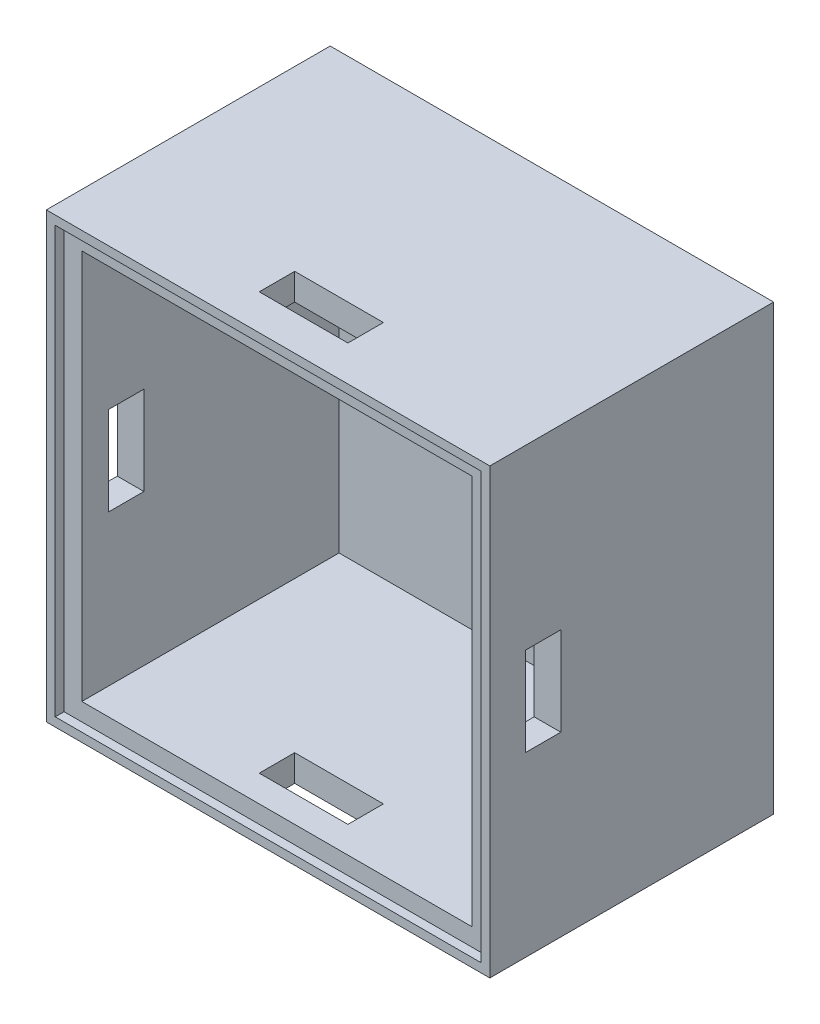
SolidWorks part; units mm, degrees
ref_plane "정면" through (0, 0, 0) normal (0, 0, 1) x (1, 0, 0)
ref_plane "윗면" through (0, 0, 0) normal (0, 1, 0) x (1, 0, 0)
ref_plane "우측면" through (0, 0, 0) normal (1, 0, 0) x (0, 0, -1)
sketch "스케치1" plane through (0, 0, 0) normal (0, 0, 1) x (1, 0, 0)
  line L1 (-125, 125) -> (125, 125)
  line L2 (-125, 125) -> (-125, -125)
  line L3 (-125, -125) -> (125, -125)
  line L4 (125, 125) -> (125, -125)
  line L5 (-125, 125) -> (125, -125) construction
  line L6 (-125, -125) -> (125, 125) construction
  point P0 (0, 0)
  dimension "D1" = 250
  dimension "D2" = 250
extrude "보스-돌출1" add sketch "스케치1" along normal blind 10 contours L1 L4 L3 L2
sketch "스케치2" plane through (0, 0, 0) normal (0, 0, -1) x (-1, 0, 0)
  line L1 (-50, 50) -> (50, 50)
  line L2 (-50, 50) -> (-50, -50)
  line L3 (-50, -50) -> (50, -50)
  line L4 (50, 50) -> (50, -50)
  line L5 (-50, 50) -> (50, -50) construction
  line L6 (-50, -50) -> (50, 50) construction
  line L7 (-127.5, 127.5) -> (127.5, 127.5)
  line L8 (-127.5, 127.5) -> (-127.5, -127.5)
  line L9 (-127.5, -127.5) -> (127.5, -127.5)
  line L10 (127.5, 127.5) -> (127.5, -127.5)
  line L11 (-127.5, 127.5) -> (127.5, -127.5) construction
  line L12 (-127.5, -127.5) -> (127.5, 127.5) construction
  line L13 (-107.5, 107.5) -> (107.5, 107.5)
  line L14 (-107.5, 107.5) -> (-107.5, -107.5)
  line L15 (-107.5, -107.5) -> (107.5, -107.5)
  line L16 (107.5, 107.5) -> (107.5, -107.5)
  line L17 (-107.5, 107.5) -> (107.5, -107.5) construction
  line L18 (-107.5, -107.5) -> (107.5, 107.5) construction
  point P0 (0, 0)
  point P6 (0, 0)
  point P11 (0, 0)
  line M3 (125, -125) -> (125, 125)
  line M4 (125, 125) -> (-125, 125)
  line M5 (-125, 125) -> (-125, -125)
  line M6 (-125, -125) -> (125, -125)
  dimension "D1" = 100
  dimension "D2" = 100
  dimension "D3" = 3.5355
  dimension "D4" = 20
  dimension "D5" = 20
extrude "보스-돌출2" add sketch "스케치2" along normal blind 5 contours L13 L16 L15 L14 M6 M3 M4 M5 | L4 L1 L2 L3 region at (0, 0, 0) region at (0, -121.4645, 0)
sketch "스케치3" plane through (0, 0, 10) normal (0, 0, 1) x (1, 0, 0)
  line L1 (-125, 125) -> (125, 125)
  line L2 (-125, 125) -> (-125, -125)
  line L3 (-125, -125) -> (125, -125)
  line L4 (125, 125) -> (125, -125)
  line L5 (-125, 125) -> (125, -125) construction
  line L6 (-125, -125) -> (125, 125) construction
  line L7 (-125, 125) -> (125, 125)
  line L8 (-125, 125) -> (-125, -125)
  line L9 (-125, -125) -> (125, -125)
  line L10 (125, 125) -> (125, -125)
  line L11 (-125, 125) -> (125, -125) construction
  line L12 (-125, -125) -> (125, 125) construction
  point P0 (0, 0)
  point P7 (0, 0)
  line M9 (-125, 125) -> (-125, -125)
  line M10 (-125, -125) -> (125, -125)
  line M11 (125, -125) -> (125, 125)
  line M12 (125, 125) -> (-125, 125)
  dimension "D1" = 250
extrude "보스-돌출3" add sketch "스케치3" along normal blind 150 contours M12 M9 M10 M11 region at (0, 0, 10)
sketch "스케치4" plane through (0, 0, 160) normal (0, 0, 1) x (1, 0, 0)
  line L1 (-110, 110) -> (110, 110)
  line L2 (-110, 110) -> (-110, -110)
  line L3 (-110, -110) -> (110, -110)
  line L4 (110, 110) -> (110, -110)
  line L5 (-110, 110) -> (110, -110) construction
  line L6 (-110, -110) -> (110, 110) construction
  point P0 (0, 0)
  dimension "D1" = 220
  dimension "D2" = 220
extrude "컷-돌출1" cut sketch "스케치4" against normal blind 150 contours L2 L3 L4 L1
sketch "스케치5" plane through (-125, 0, 0) normal (-1, 0, 0) x (0, 0, 1)
  text T0 "\r\n\r\n\r\nfront" font "Century Gothic" height 20
extrude "컷-돌출2" cut sketch "스케치5" against normal blind 4
ref_plane "평면1" through (0, 0, 150) normal (0, 0, -1) x (-1, 0, 0)
sketch "스케치6" plane through (-125, 0, 0) normal (-1, 0, 0) x (0, 0, 1)
  line L0 (160, -125) -> (-5, -125) construction
  line L1 (120, 25) -> (140, 25)
  line L2 (120, 25) -> (120, -25)
  line L3 (120, -25) -> (140, -25)
  line L4 (140, 25) -> (140, -25)
  line L5 (120, 25) -> (140, -25) construction
  line L6 (120, -25) -> (140, 25) construction
  line L7 (160, 125) -> (-5, 125) construction
  line L9 (160, 125) -> (160, -125) construction
  point P0 (130, 0)
  dimension "D1" = 100
  dimension "D2" = 100
  dimension "D3" = 20
  dimension "D4" = 20
extrude "컷-돌출3" cut sketch "스케치6" against normal through all
sketch "스케치7" plane through (0, 0, 0) normal (0, 1, 0) x (1, 0, 0)
  line L0 (0, 0) -> (0, -331.8175) construction
pattern_circular "원형 패턴1" count 2 every 90 about axis through (0, 0, 0) along (0, 0, 1) of "컷-돌출3" reverse direction yes
sketch "스케치11" plane through (0, 0, 160) normal (0, 0, 1) x (1, 0, 0)
  line L0 (125, 125) -> (-125, 125) construction
  line L1 (-120, 120) -> (120, 120)
  line L2 (-120, 120) -> (-120, -120)
  line L3 (-120, -120) -> (120, -120)
  line L4 (120, 120) -> (120, -120)
  line L5 (-120, 120) -> (120, -120) construction
  line L6 (-120, -120) -> (120, 120) construction
  line L7 (125, -125) -> (125, 125) construction
  point P0 (0, 0)
  dimension "D1" = 5
  dimension "D2" = 5
extrude "컷-돌출5" cut sketch "스케치11" against normal blind 5
sketch "스케치12" plane through (0, 0, -5) normal (0, 0, -1) x (-1, 0, 0)
  line L0 (125, 125) -> (-125, 125) construction
  line L1 (-120, 120) -> (120, 120)
  line L2 (-120, 120) -> (-120, -120)
  line L3 (-120, -120) -> (120, -120)
  line L4 (120, 120) -> (120, -120)
  line L5 (-120, 120) -> (120, -120) construction
  line L6 (-120, -120) -> (120, 120) construction
  line L7 (-125, 125) -> (-125, -125) construction
  point P0 (0, 0)
  dimension "D1" = 5
  dimension "D2" = 5
extrude "컷-돌출6" cut sketch "스케치12" against normal blind 5 flip side to cut
